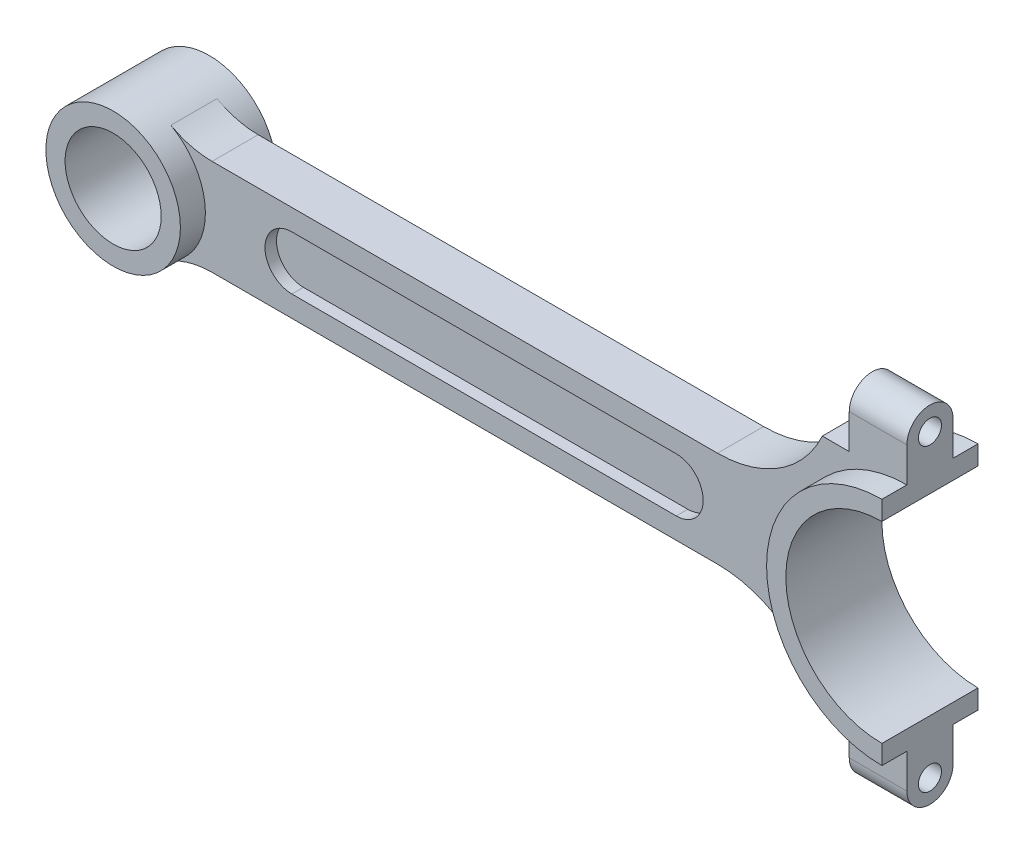
SolidWorks part; units mm, degrees
ref_plane "Front Plane" through (0, 0, 0) normal (0, 0, 1) x (1, 0, 0)
ref_plane "Top Plane" through (0, 0, 0) normal (0, 1, 0) x (1, 0, 0)
ref_plane "Right Plane" through (0, 0, 0) normal (1, 0, 0) x (0, 0, -1)
sketch "Sketch1" plane through (0, 0, 0) normal (0, 0, 1) x (1, 0, 0)
  line L0 (0, 0) -> (555.1951, 0) construction
  line L1 (400, 50) -> (400, 60)
  line L2 (400, -50) -> (400, -60)
  circle A0 centre (0, 0) radius 35
  circle A1 centre (0, 0) radius 25
  arc A2 (400, 50) -> (400, -50) centre (400, 0) ccw
  arc A3 (400, 60) -> (400, -60) centre (400, 0) ccw
  dimension "D1" = 50
  dimension "D2" = 70
  dimension "D3" = 120
  dimension "D4" = 100
  dimension "D5" = 400
extrude "Boss-Extrude1" add sketch "Sketch1" along normal mid plane 50
sketch "Sketch2" plane through (0, 0, 0) normal (0, 0, 1) x (1, 0, 0)
  line L0 (35, 0) -> (340, 0) construction
  line L1 (35, 25) -> (340, 25)
  line L2 (400, 60) -> (356, 60)
  line L3 (356, 60) -> (340, 25)
  line L4 (35, 25) -> (24.4949, 25)
  line L5 (35, -25) -> (24.4949, -25)
  line L6 (356, -60) -> (340, -25)
  line L7 (400, -60) -> (356, -60)
  line L8 (35, -25) -> (340, -25)
  circle A0 centre (0, 0) radius 35 construction
  arc A1 (400, 60) -> (400, -60) centre (400, 0) ccw construction
  arc A2 (24.4949, -25) -> (24.4949, 25) centre (0, 0) ccw
  arc A3 (400, 60) -> (400, -60) centre (400, 0) ccw
  dimension "D2" = 44
  dimension "D1" = 25
extrude "Boss-Extrude3" add sketch "Sketch2" along normal mid plane 24
fillet "Fillet1" radius 44 2 edges at (24.4949, -25, 0) (24.4949, 25, 0)
fillet "Fillet2" radius 60 2 edges at (340, -25, 0) (340, 25, 0)
sketch "Sketch3" plane through (400, 0, 0) normal (1, 0, 0) x (0, 0, -1)
  line L0 (0, 90) -> (-48.2065, 90) construction
  line L1 (-25, 60) -> (-12, 60) construction
  line L2 (-12, 78) -> (-12, 60)
  line L3 (-12, 60) -> (12, 60)
  line L4 (12, 60) -> (12, 78)
  arc A0 (12, 78) -> (-12, 78) centre (0, 78) ccw
  circle A1 centre (0, 78) radius 6
  dimension "D1" = 24
  dimension "D2" = 12
  dimension "D3" = 30
extrude "Boss-Extrude4" add sketch "Sketch3" against normal blind 30
mirror "Mirror1" about plane through (0, 0, 0) normal (0, 1, 0) of "Boss-Extrude4"
sketch "Sketch4" plane through (0, 0, 12) normal (0, 0, 1) x (1, 0, 0)
  line L0 (0, 0) -> (340, 0) construction
  line L1 (280, 0) -> (80, 0) construction
  line L2 (280, -14) -> (80, -14)
  line L3 (280, 14) -> (80, 14)
  arc A0 (400, 60) -> (400, -60) centre (400, 0) ccw construction
  arc A1 (280, -14) -> (280, 14) centre (280, 0) ccw
  arc A2 (80, 14) -> (80, -14) centre (80, 0) ccw
  point P8 (180, 0)
  dimension "D3" = 14
  dimension "D1" = 200
  dimension "D2" = 80
extrude "Cut-Extrude1" cut sketch "Sketch4" against normal blind 6
mirror "Mirror2" about plane through (0, 0, 0) normal (0, 0, 1) of "Cut-Extrude1"
